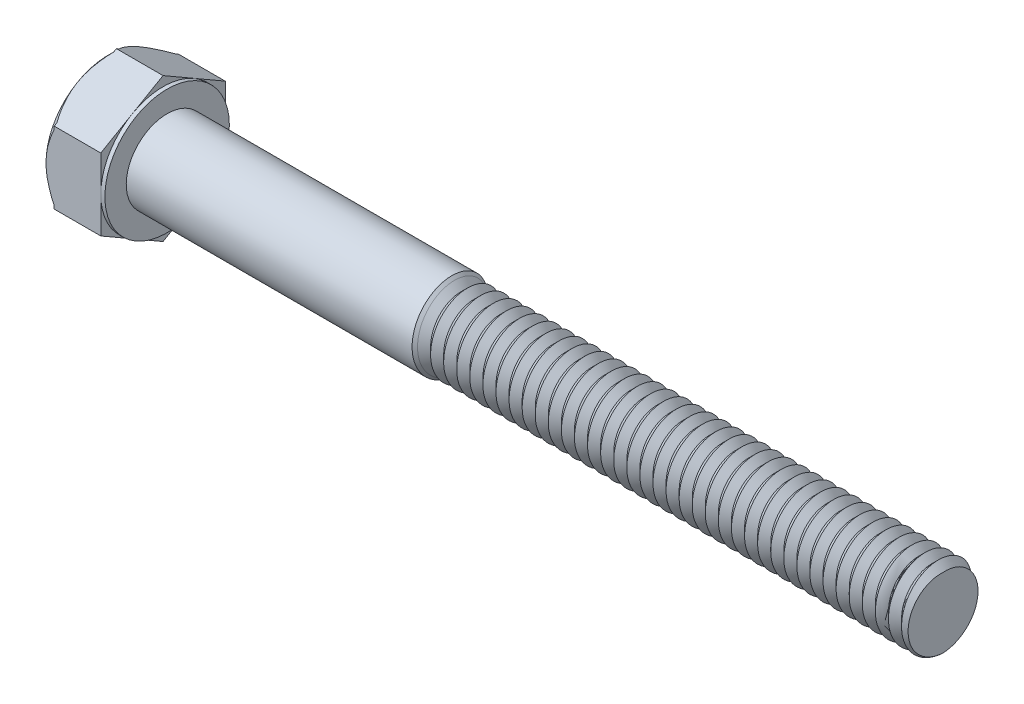
SolidWorks part; units mm, degrees
material "Plain Carbon Steel"
ref_plane "Front Plane" through (0, 0, 0) normal (0, 0, 1) x (1, 0, 0)
ref_plane "Top Plane" through (0, 0, 0) normal (0, 1, 0) x (1, 0, 0)
ref_plane "Right Plane" through (0, 0, 0) normal (1, 0, 0) x (0, 0, -1)
sketch "Sketch3" plane through (0, 0, 0) normal (1, 0, 0) x (0, 0, -1)
  line L1 (0, -4.395) -> (3.8062, -2.1975)
  line L2 (3.8062, -2.1975) -> (3.8062, 2.1975)
  line L3 (3.8062, 2.1975) -> (0, 4.395)
  line L4 (0, 4.395) -> (-3.8062, 2.1975)
  line L5 (-3.8062, 2.1975) -> (-3.8062, -2.1975)
  line L6 (-3.8062, -2.1975) -> (0, -4.395)
  circle A0 centre (0, 0) radius 3.8062 construction
  dimension "D1" = 8.79
extrude "Boss-Extrude1" add sketch "Sketch3" along normal mid plane 3.35
sketch "Sketch4" plane through (1.675, 0, 0) normal (1, 0, 0) x (0, 0, -1)
  circle A0 centre (0, 0) radius 2.5
  dimension "D1" = 5
extrude "Boss-Extrude2" add sketch "Sketch4" along normal blind 47.7
sketch "Sketch5" plane through (0, 0, 0) normal (0, 0, 1) x (1, 0, 0)
  line L0 (49.9407, 2.5) -> (49.375, 1.9343)
  line L1 (49.375, 1.9343) -> (48.8093, 2.5)
  line L2 (49.375, 2.5) -> (1.675, 2.5) construction
  line L3 (48.8093, 2.5) -> (49.375, 3.0657)
  line L4 (49.375, 3.0657) -> (49.9407, 2.5)
  line L5 (49.375, -2.5) -> (49.375, 2.5) construction
  dimension "D1" = 45
  dimension "D2" = 0.8
sketch "Sketch6" plane through (49.375, 0, 0) normal (1, 0, 0) x (0, 0, -1)
  circle A0 centre (0, 0) radius 2.5
curve "Helix/Spiral1" pitch 0.8 height 30 radius 2.5 centre (49.375, 0, 0) axis (-1, 0, 0) start towards (0, 0.7071, 0.7071)
sweep "Cut-Sweep1" cut profiles "Sketch5" path "Helix/Spiral1" align with end faces yes
sketch "Sketch7" plane through (-1.675, 0, 0) normal (-1, 0, 0) x (0, 0, 1)
  circle A0 centre (0, 0) radius 3.8062
extrude "Cut-Extrude3" cut sketch "Sketch7" against normal blind 0.5 draft 45 flip side to cut
sketch "Sketch8" plane through (1.675, 0, 0) normal (1, 0, 0) x (0, 0, -1)
  circle A0 centre (0, 0) radius 3.8062
extrude "Boss-Extrude3" add sketch "Sketch8" along normal blind 0.25
